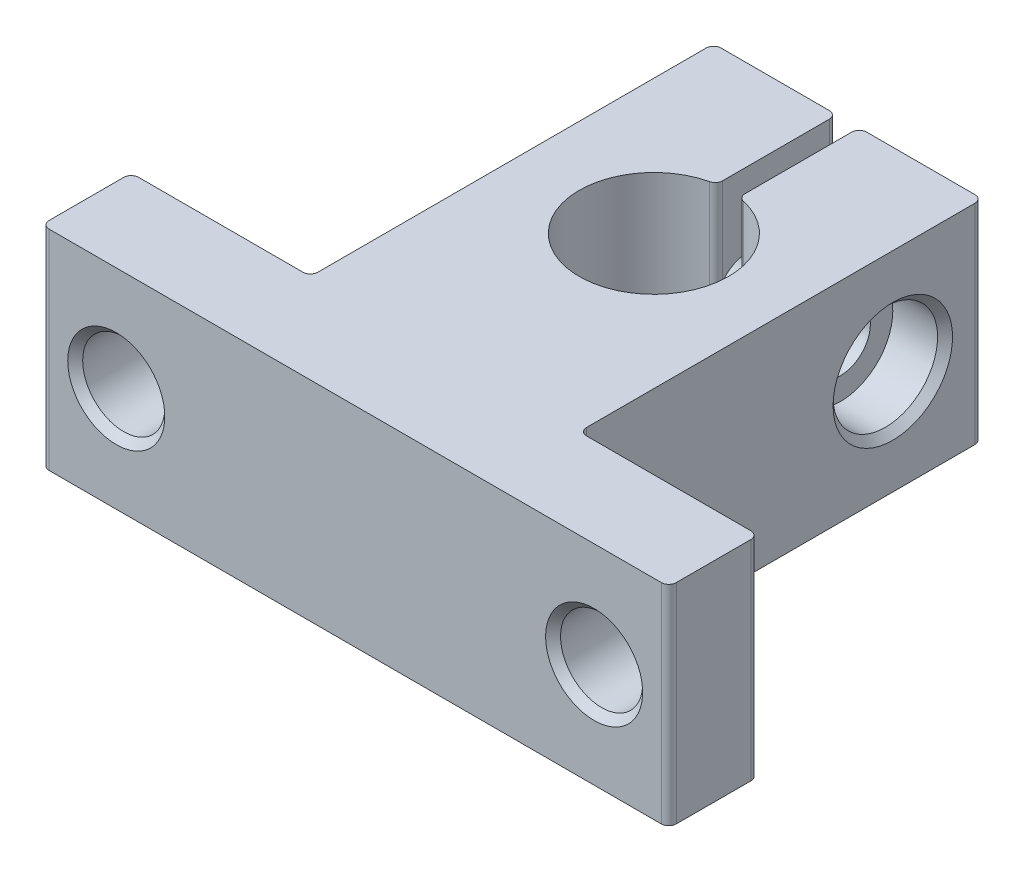
SolidWorks part; units mm, degrees
ref_plane "Front Plane" through (0, 0, 0) normal (0, 0, 1) x (1, 0, 0)
ref_plane "Top Plane" through (0, 0, 0) normal (0, 1, 0) x (1, 0, 0)
ref_plane "Right Plane" through (0, 0, 0) normal (1, 0, 0) x (0, 0, -1)
sketch "Sketch1" plane through (0, 0, 0) normal (0, 1, 0) x (1, 0, 0)
  line L1 (-21, -3) -> (21, -3)
  line L2 (-21, -3) -> (-21, 3)
  line L3 (-21, 3) -> (21, 3)
  line L4 (21, -3) -> (21, 3)
  line L5 (-21, -3) -> (21, 3) construction
  line L6 (-21, 3) -> (21, -3) construction
  line L7 (-9, -30) -> (9, -30)
  line L8 (-9, -30) -> (-9, 30)
  line L9 (-9, 30) -> (9, 30)
  line L10 (9, -30) -> (9, 30)
  line L11 (-9, -30) -> (9, 30) construction
  line L12 (-9, 30) -> (9, -30) construction
  line L13 (-0.75, 40.0493) -> (0.75, 40.0493)
  line L14 (-0.75, 40.0493) -> (-0.75, 19.9507)
  line L15 (-0.75, 19.9507) -> (0.75, 19.9507)
  line L16 (0.75, 40.0493) -> (0.75, 19.9507)
  line L17 (-0.75, 40.0493) -> (0.75, 19.9507) construction
  line L18 (-0.75, 19.9507) -> (0.75, 40.0493) construction
  circle A0 centre (0, 17) radius 5
  point P0 (0, 0)
  point P6 (0, 0)
  point P13 (0, 30)
  dimension "D4" = 10
  dimension "D1" = 6
  dimension "D2" = 42
  dimension "D3" = 18
  dimension "D5" = 27
  dimension "D6" = 14
  dimension "D7" = 1.5
extrude "Boss-Extrude1" add sketch "Sketch1" along normal blind 14 contours A0 L14 L9 L8 L3 L10 L16 | L4 L3 L2 L1 region at (-8.6755, 0, -16.5)
sketch "Sketch2" plane through (0, 0, -3) normal (0, 0, -1) x (-1, 0, 0)
  line L0 (-21, 7) -> (21, 7) construction
  line L1 (-21, 14) -> (-21, 0) construction
  line L2 (21, 14) -> (21, 0) construction
  line L3 (-16, 7) -> (16, 7)
  circle A0 centre (-16, 7) radius 2.75
  circle A1 centre (16, 7) radius 2.75
  point P9 (0, 7)
  dimension "D2" = 5.5
  dimension "D3" = 5.5
  dimension "D1" = 32
extrude "Cut-Extrude1" cut sketch "Sketch2" against normal blind 14 contours L0 A0 L3 | A0 | A1 region at (16, 5.8329, -3)
sketch "Sketch3" plane through (9, 0, 0) normal (1, 0, 0) x (0, 0, -1)
  line L0 (30, 7) -> (24, 7) construction
  line L1 (30, 14) -> (30, 0) construction
  circle A0 centre (24, 7) radius 2
  dimension "D1" = 4
  dimension "D2" = 6
extrude "Cut-Extrude2" cut sketch "Sketch3" against normal through all
sketch "Sketch4" plane through (9, 0, 0) normal (1, 0, 0) x (0, 0, -1)
  circle A0 centre (24, 7) radius 3.5
  dimension "D1" = 7
extrude "Cut-Extrude3" cut sketch "Sketch4" against normal blind 3.5
fillet "Fillet1" radius 0.5 12 edges at (0.75, 7, -30) (-0.75, 7, -30) (-0.75, 7, -21.9434) (0.75, 7, -21.9434) (21, 7, 3) (-21, 7, 3) (21, 7, -3) (9, 7, -3) (-21, 7, -3) (-9, 7, -3) (-9, 7, -30) (9, 7, -30)
chamfer "Chamfer1" distance 0.5 angle 45 6 edges at (-9, 7, -22) (-18.75, 7, 3) (13.25, 7, 3) (-18.75, 7, -3) (13.25, 7, -3) (9, 7, -27.5)
